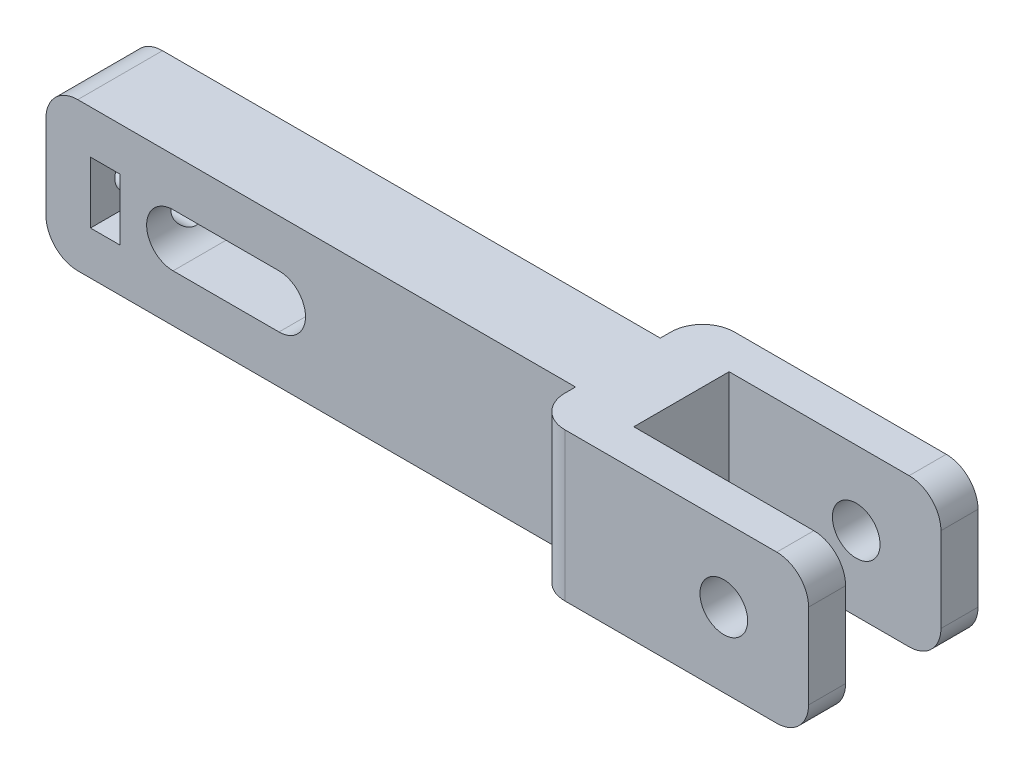
SolidWorks part; units mm, degrees
ref_plane "Front Plane" through (0, 0, 0) normal (0, 0, 1) x (1, 0, 0)
ref_plane "Top Plane" through (0, 0, 0) normal (0, 1, 0) x (1, 0, 0)
ref_plane "Right Plane" through (0, 0, 0) normal (1, 0, 0) x (0, 0, -1)
sketch "Sketch1" plane through (0, 0, 0) normal (0, 1, 0) x (1, 0, 0)
  line L0 (0, -4) -> (0, 4)
  line L1 (76, 8) -> (50, 8)
  line L2 (50, 8) -> (50, -4)
  line L3 (50, -4) -> (0, -4)
  line L4 (76, 8) -> (76, 4.5)
  line L5 (76, 4.5) -> (56, 4.5)
  line L6 (56, 4.5) -> (56, -4.5)
  line L7 (56, -4.5) -> (76, -4.5)
  line L8 (76, -4.5) -> (76, -8)
  line L9 (0, 0) -> (56, 0) construction
  line L12 (76, -8) -> (50, -8)
  line L13 (50, -8) -> (50, 4)
  line L14 (50, 4) -> (0, 4)
  point P2 (0, 0)
  dimension "D1" = 50
  dimension "D2" = 8
  dimension "D3" = 9
  dimension "D4" = 3.5
  dimension "D5" = 20
  dimension "D6" = 26
  dimension "D7" = 16
extrude "Boss-Extrude1" add sketch "Sketch1" along normal mid plane 14 contours L2 L9 L6 L5 L4 L1 | L9 L13 L12 L8 L7 L6 | L0 L9 L2 L14 | L9 L0 L3 L13 region at (25, 0, 2) region at (25, 0, -2) region at (60.7119, 0, 5.3347) region at (60.7119, 0, -5.3347)
hole_wizard "M4 Clearance Hole1" positions "Sketch3" profile "Sketch4" hole size "M4" standard "ANSI Metric" end condition through all
sketch "Sketch3" plane through (0, 0, -8) normal (0, 0, -1) x (-1, 0, 0)
  line L0 (-68, 0) -> (-76, 0) construction
  line L2 (-76, 7) -> (-76, -7) construction
  point P0 (-68, 0)
  point P8 (-76, 0)
  dimension "D1" = 8
sketch "Sketch4" plane through (68, 0, -8) normal (1, 0, 0) x (0, 1, 0)
  line L0 (0, 0) -> (0, 16)
  line L1 (0, 16) -> (2.25, 16)
  line L2 (2.25, 16) -> (2.25, 0)
  line L5 (2.25, 0) -> (0, 0)
  line L11 (0, -6.35) -> (0, 107.95) construction
  dimension "Thru Hole Dia." = 4.5
  dimension "Thru Hole Depth" = 16
sketch "Sketch6" plane through (0, 0, -4) normal (0, 0, -1) x (-1, 0, 0)
  line L0 (-12, 0) -> (-22, 0) construction
  line L1 (-12, -2.5) -> (-22, -2.5)
  line L2 (-12, 2.5) -> (-22, 2.5)
  line L3 (-12, 0) -> (0, 0) construction
  line L4 (-76, 7) -> (-76, -7) construction
  arc A0 (-12, -2.5) -> (-12, 2.5) centre (-12, 0) ccw
  arc A1 (-22, 2.5) -> (-22, -2.5) centre (-22, 0) ccw
  point P3 (-17, 0)
  dimension "D1" = 2.5
  dimension "D2" = 10
  dimension "D3" = 54
extrude "Cut-Extrude1" cut sketch "Sketch6" against normal through all both and the other way through all
ref_plane "Plane1" through (7, 0, 0) normal (-1, 0, 0) x (0, 0, 1)
sketch "Sketch7" plane through (7, 0, 0) normal (-1, 0, 0) x (0, 0, 1)
  line L1 (0, 0) -> (-0.25, 0) construction
  line L2 (4, 2.9) -> (-1.9243, 2.9)
  line L3 (-1.9243, 2.9) -> (-3.5986, 0)
  line L4 (-3.5986, 0) -> (-1.9243, -2.9)
  line L5 (-1.9243, -2.9) -> (4, -2.9)
  line L7 (4, 7) -> (4, -7) construction
  line L8 (4, 2.9) -> (4, -2.9)
  line L11 (2.4001, -1.2098) -> (3.2373, 0.2402) [skipped]
  line L12 (2.4001, 1.2098) -> (1.563, 2.6598) [skipped]
  point P2 (2.2057, -2.8962)
  point P3 (3.8999, -2.9)
  point P7 (0, 0)
  point P9 (0.1675, -4.1489)
  point P10 (3.9127, 2.9)
  dimension "D1" = 5.8
  dimension "D3" = 0.25
extrude "Cut-Extrude2" cut sketch "Sketch7" along normal blind 2.8 contours L8 L2 L3 L4 L5 region at (7, 0, 0.602)
hole_wizard "M3 Clearance Hole1" positions "3DSketch3" profile "Sketch10" hole size "M3" standard "ANSI Metric"
sketch3d "3DSketch3"
  point P0 (0, 0, 0)
  point P3 (0, 0, 0)
sketch "Sketch10" plane through (0, 0, 0) normal (0, 1, 0) x (0, 0, 1)
  line L0 (0, 0) -> (0, 17.0215)
  line L1 (0, 17.0215) -> (1.7, 16)
  line L2 (1.7, 16) -> (1.7, 0)
  line L5 (1.7, 0) -> (0, 0)
  line L10 (0, 17.0215) -> (-1.7, 16) construction
  line L11 (0, -6.35) -> (0, 107.95) construction
  dimension "Hole Dia." = 3.4
  dimension "Hole Depth" = 16
  dimension "Drill Angle" = 118
fillet "Fillet1" radius 3 8 edges at (50, 0, 8) (50, 0, -8) (0, -7, 0) (0, 7, 0) (76, 7, 6.25) (76, -7, 6.25) (76, -7, -6.25) (76, 7, -6.25)
